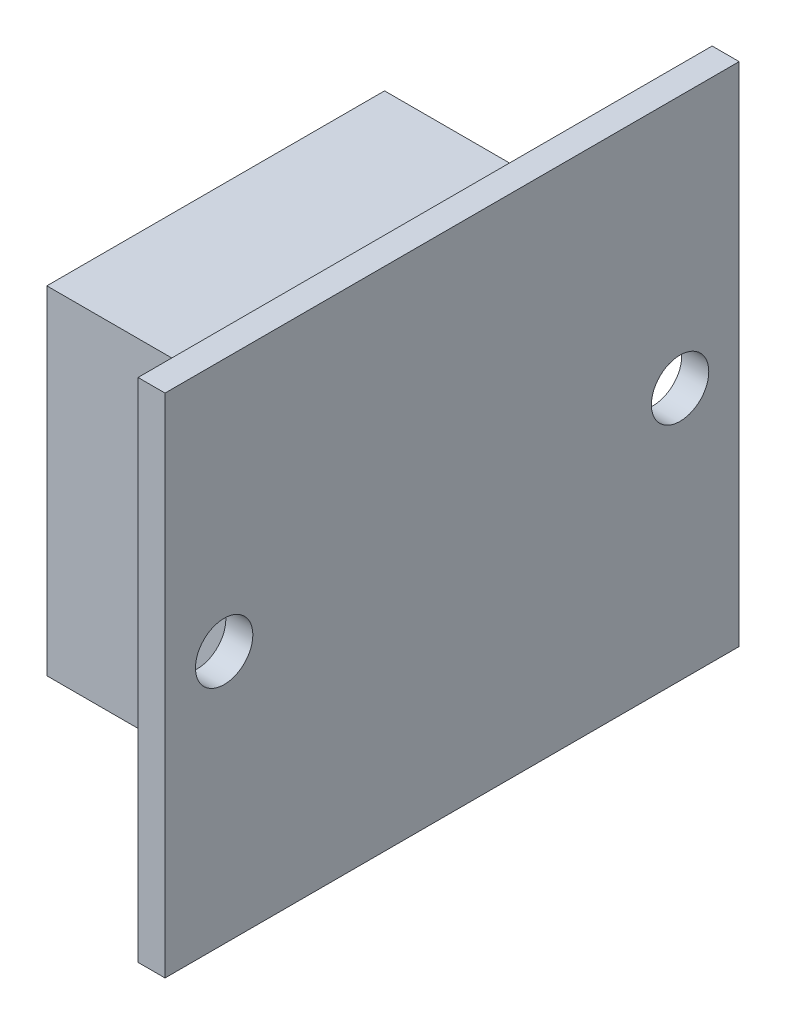
SolidWorks part; units mm, degrees
ref_plane "Front Plane" through (0, 0, 0) normal (0, 0, 1) x (1, 0, 0)
ref_plane "Top Plane" through (0, 0, 0) normal (0, 1, 0) x (1, 0, 0)
ref_plane "Right Plane" through (0, 0, 0) normal (1, 0, 0) x (0, 0, -1)
sketch "Plate Sketch" plane through (0, 0, 0) normal (1, 0, 0) x (0, 0, -1)
  line L0 (17, -60) -> (17, -30)
  line L1 (17, -30) -> (-17, -30)
  line L2 (-17, -30) -> (-17, -60)
  line L3 (-17, -60) -> (17, -60)
  circle A0 centre (13.5, -45) radius 1.7
  circle A1 centre (-13.5, -45) radius 1.7
extrude "Plate" add sketch "Plate Sketch" against normal blind 1.6 from offset 91.6 offset against normal yes
ref_axis "Engine Axis" through (-90.9, 0, 0) along (-1, 0, 0)
sketch "Matek M10Q-5883 Sketch" plane through (0, 0, 0) normal (1, 0, 0) x (0, 0, -1)
  line L0 (10, -55) -> (10, -35)
  line L1 (10, -35) -> (-10, -35)
  line L2 (-10, -35) -> (-10, -55)
  line L3 (-10, -55) -> (10, -55)
extrude "Matek M10Q-5883" add sketch "Matek M10Q-5883 Sketch" against normal blind 12.4 from offset 93.2 offset against normal yes
